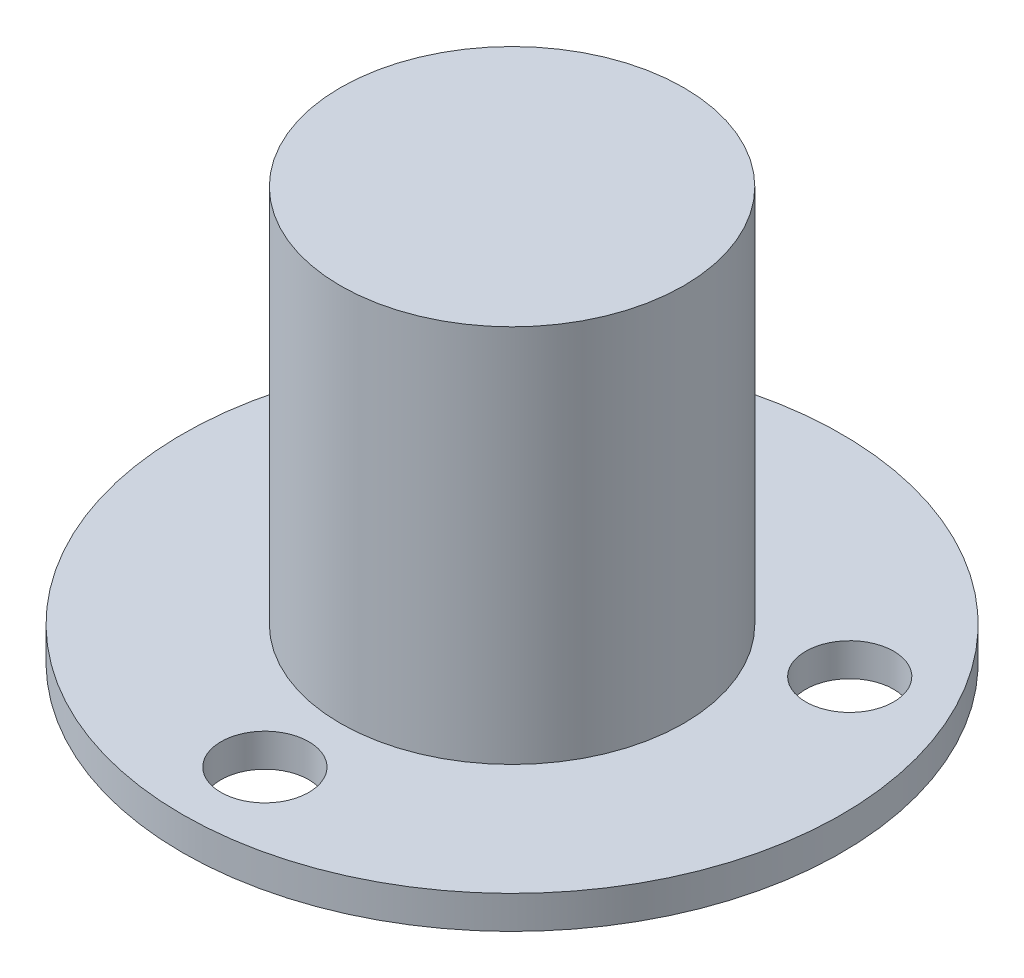
SolidWorks part; units mm, degrees
ref_plane "Front Plane" through (0, 0, 0) normal (0, 0, 1) x (1, 0, 0)
ref_plane "Top Plane" through (0, 0, 0) normal (0, 1, 0) x (1, 0, 0)
ref_plane "Right Plane" through (0, 0, 0) normal (1, 0, 0) x (0, 0, -1)
sketch "Sketch1" plane through (0, 0, 0) normal (0, 1, 0) x (1, 0, 0)
  circle A0 centre (0, 0) radius 12
  dimension "D1" = 24
extrude "Boss-Extrude1" add sketch "Sketch1" along normal blind 1.2
sketch "Sketch2" plane through (0, 1.2, 0) normal (0, 1, 0) x (1, 0, 0)
  circle A0 centre (0, 0) radius 6.25
  dimension "D1" = 12.5
extrude "Boss-Extrude2" add sketch "Sketch2" along normal blind 13.8
sketch "Sketch3" plane through (0, 0, 0) normal (0, -1, 0) x (1, 0, 0)
  circle A0 centre (0, 0) radius 2.5
  dimension "D1" = 5
extrude "Boss-Extrude3" add sketch "Sketch3" along normal blind 1.5
sketch "Sketch4" plane through (0, 0, 0) normal (0, -1, 0) x (1, 0, 0)
  line L0 (0, 0) -> (0, 9) construction
  circle A0 centre (0, 9) radius 1.6
  circle A1 centre (7.7942, -4.5) radius 1.6
  circle A2 centre (-7.7942, -4.5) radius 1.6
  point P11 (0, 0)
  dimension "D2" = 3.2
  dimension "D1" = 9
  dimension "D3" = 3
extrude "Cut-Extrude1" cut sketch "Sketch4" against normal up to surface (1.2 mm away) up to face at (0, 1.2, 6.25)
